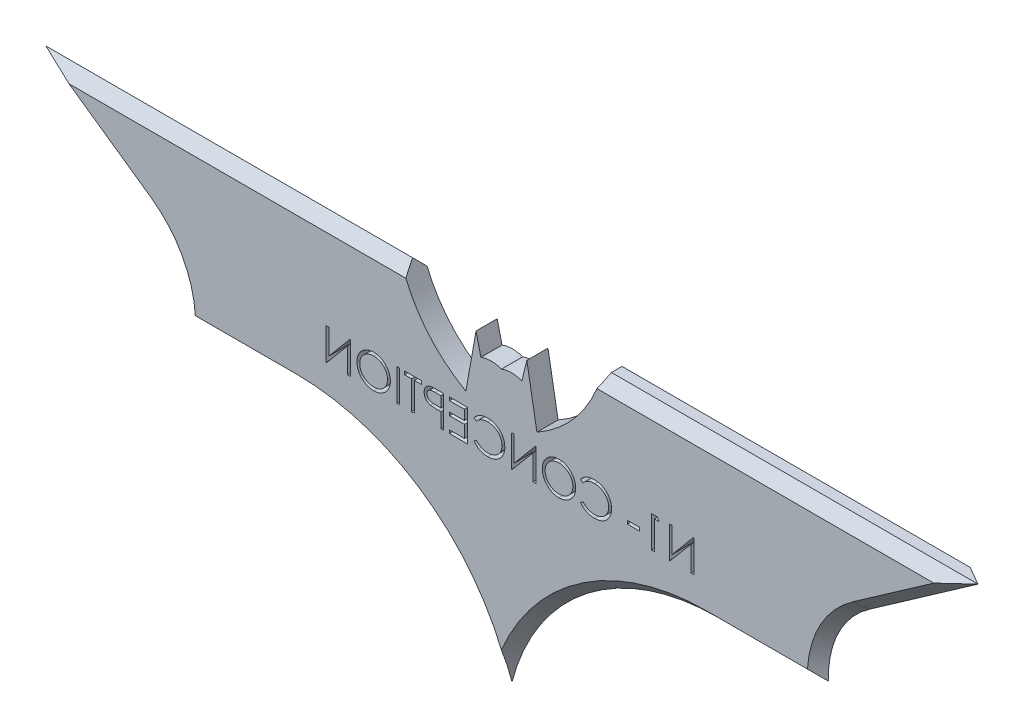
SolidWorks part; units mm, degrees
ref_plane "Front Plane" through (0, 0, 0) normal (0, 0, 1) x (1, 0, 0)
ref_plane "Top Plane" through (0, 0, 0) normal (0, 1, 0) x (1, 0, 0)
ref_plane "Right Plane" through (0, 0, 0) normal (1, 0, 0) x (0, 0, -1)
sketch "Sketch1" plane through (0, 0, 0) normal (0, 0, 1) x (1, 0, 0)
  line L0 (0, 0) -> (0, 35382.3844) construction
  line L1 (-9.681, 0) -> (-12, 9.5898)
  line L2 (-12, 9.5898) -> (-16.7608, -17.4102)
  line L3 (-46.9179, 19.5898) -> (-220, 19.5898)
  line L4 (-220, 19.5898) -> (-168.6141, -16.3911)
  line L5 (-149.4767, -55.4102) -> (-96.8246, -55.4102)
  line L6 (46.9179, 19.5898) -> (220, 19.5898)
  line L7 (220, 19.5898) -> (168.6141, -16.3911)
  line L8 (149.4767, -55.4102) -> (96.8246, -55.4102)
  line L9 (12, 9.5898) -> (16.7608, -17.4102)
  line L10 (9.681, 0) -> (12, 9.5898)
  arc A0 (0, 0) -> (-9.681, 0) centre (-4.8405, -12.5676) ccw
  arc A1 (-16.7608, -17.4102) -> (-46.9179, 19.5898) centre (14.9051, 39.189) cw
  arc A2 (-168.6141, -16.3911) -> (-149.4767, -55.4102) centre (-194.425, -53.2529) cw
  arc A3 (-96.8246, -55.4102) -> (0, -130.4102) centre (-96.8246, -155.4102) cw
  arc A4 (0, 0) -> (9.681, 0) centre (4.8405, -12.5676) cw
  arc A5 (96.8246, -55.4102) -> (0, -130.4102) centre (96.8246, -155.4102) ccw
  arc A6 (168.6141, -16.3911) -> (149.4767, -55.4102) centre (194.425, -53.2529) ccw
  arc A7 (16.7608, -17.4102) -> (46.9179, 19.5898) centre (-14.9051, 39.189) ccw
  dimension "D1" = 24
  dimension "D4" = 100
  dimension "D11" = 45
  dimension "D2" = 40
  dimension "D3" = 220
  dimension "D5" = 75
  dimension "D6" = 75
  dimension "D7" = 35
  dimension "D8" = 37
  dimension "D9" = 10
  dimension "D10" = 80
extrude "Boss-Extrude1" add sketch "Sketch1" along normal blind 10
chamfer "Chamfer1" distance 5 angle 45 19 edges at (-133.4589, 19.5898, 10) (-194.307, 1.5994, 10) (-154.0228, -33.4372, 10) (-123.1507, -55.4102, 10) (-35.5873, -76.3533, 10) (133.4589, 19.5898, 10) (194.307, 1.5994, 10) (154.0228, -33.4372, 10) (123.1507, -55.4102, 10) (35.5873, -76.3533, 10) (194.307, 1.5994, 0) (154.0228, -33.4372, 0) (123.1507, -55.4102, 0) (35.5873, -76.3533, 0) (-133.4589, 19.5898, 0) (-194.307, 1.5994, 0) (-154.0228, -33.4372, 0) (-123.1507, -55.4102, 0) (-35.5873, -76.3533, 0)
sketch "Sketch2" plane through (0, 0, 0) normal (0, 0, -1) x (-1, 0, 0)
  text T0 "N1- CONCEPTION " font "Century Gothic" height 15
extrude "Cut-Extrude1" cut sketch "Sketch2" against normal blind 177
